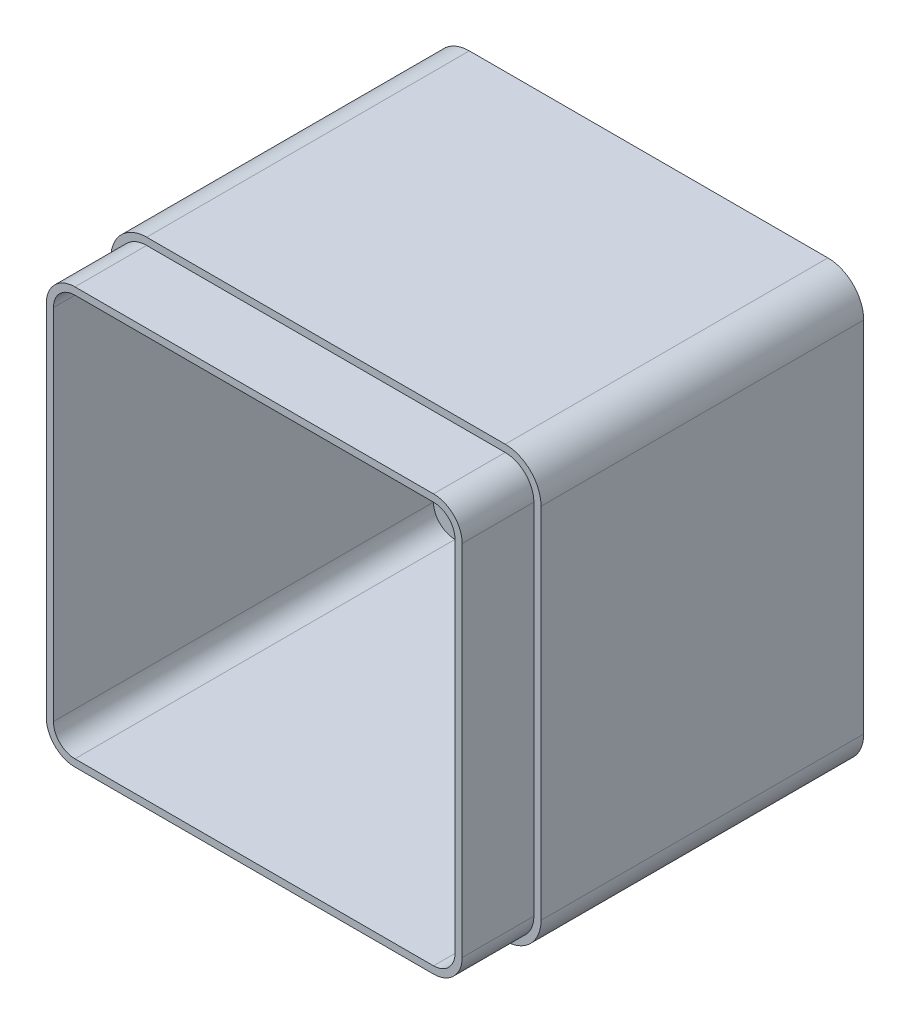
SolidWorks part; units mm, degrees
ref_plane "Front Plane" through (0, 0, 0) normal (0, 0, 1) x (1, 0, 0)
ref_plane "Top Plane" through (0, 0, 0) normal (0, 1, 0) x (1, 0, 0)
ref_plane "Right Plane" through (0, 0, 0) normal (1, 0, 0) x (0, 0, -1)
sketch "Sketch1" plane through (0, 0, 0) normal (0, 0, 1) x (1, 0, 0)
  line L1 (0, 0) -> (120, 0)
  line L2 (0, 0) -> (0, 120)
  line L3 (0, 120) -> (120, 120)
  line L4 (120, 0) -> (120, 120)
  dimension "D1" = 120
  dimension "D2" = 120
extrude "Boss-Extrude1" add sketch "Sketch1" along normal blind 90 contours L3 L4 L1 L2
fillet "Fillet1" radius 10 4 edges at (0, 0, 45) (120, 0, 45) (0, 120, 45) (120, 120, 45)
shell "Shell1" thickness 4 removed face at (60, 60, 90)
sketch "Sketch2" plane through (0, 0, 90) normal (0, 0, 1) x (1, 0, 0)
  line L8 (2, 110) -> (2, 10)
  line L9 (10, 2) -> (110, 2)
  line L10 (118, 10) -> (118, 110)
  line L11 (110, 118) -> (10, 118)
  line L12 (2, 110) -> (2, 10)
  line L13 (10, 2) -> (110, 2)
  line L14 (118, 10) -> (118, 110)
  line L15 (110, 118) -> (10, 118)
  arc A8 (2, 10) -> (10, 2) centre (10, 10) ccw
  arc A9 (110, 2) -> (118, 10) centre (110, 10) ccw
  arc A10 (118, 110) -> (110, 118) centre (110, 110) ccw
  arc A11 (10, 118) -> (2, 110) centre (10, 110) ccw
  arc A12 (2, 10) -> (10, 2) centre (10, 10) ccw
  arc A13 (110, 2) -> (118, 10) centre (110, 10) ccw
  arc A14 (118, 110) -> (110, 118) centre (110, 110) ccw
  arc A15 (10, 118) -> (2, 110) centre (10, 110) ccw
  arc M17 (10, 4) -> (4, 10) centre (10, 10) cw
  line M18 (4, 10) -> (4, 110)
  arc M19 (4, 110) -> (10, 116) centre (10, 110) cw
  line M20 (10, 116) -> (110, 116)
  arc M21 (110, 116) -> (116, 110) centre (110, 110) cw
  line M22 (116, 110) -> (116, 10)
  arc M23 (116, 10) -> (110, 4) centre (110, 10) cw
  line M24 (110, 4) -> (10, 4)
  dimension "D1" = 2
extrude "Boss-Extrude3" add sketch "Sketch2" along normal blind 20 contours M17 M24 M23 M22 M21 M20 M19 M18 | L15 A15 L12 A12 L13 A13 L14 A14 region at (60, 60, 90)
